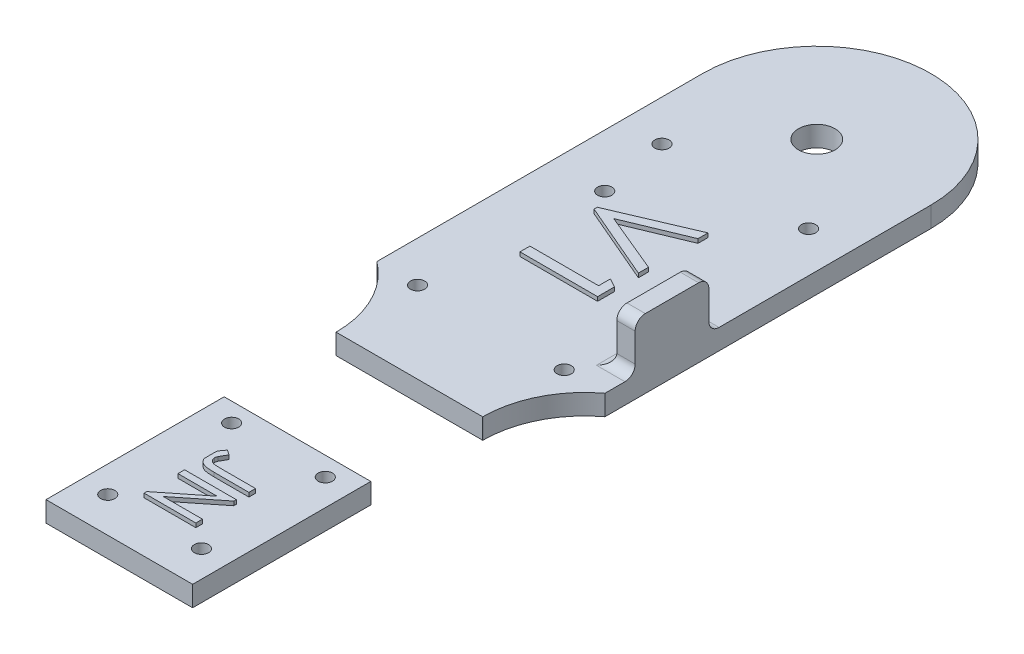
SolidWorks part; units mm, degrees
note: The reader was unsure of these and kept them because the rebuilt part matched: shared geometry of "Sketch2<10>".
ref_plane "Front Plane" through (0, 0, 0) normal (0, 0, 1) x (1, 0, 0)
ref_plane "Top Plane" through (0, 0, 0) normal (0, 1, 0) x (1, 0, 0)
ref_plane "Right Plane" through (0, 0, 0) normal (1, 0, 0) x (0, 0, -1)
sketch "Sketch2" plane through (0, 0, 0) normal (0, 1, 0) x (1, 0, 0)
  line L0 (-17.1263, -104.1263) -> (-17.1263, -4.1263)
  line L1 (-27.1263, 95.8737) -> (-27.1263, 15.8741)
  line L2 (18.8737, -104.1263) -> (18.8737, -4.1268)
  line L3 (-27.1263, 95.8737) -> (28.8737, 95.8737)
  line L4 (28.8737, 95.8737) -> (28.8737, 15.8737)
  line L5 (-17.1263, -75.3563) -> (18.8737, -75.3563)
  line L6 (-17.1263, -31.6163) -> (18.8737, -31.6163)
  line L7 (-17.1263, -4.1363) -> (18.8737, -4.1363)
  line L8 (-5.4644, -31.6163) -> (-5.4644, -75.3563)
  line L9 (-10.6263, 95.8737) -> (-10.6263, -4.1363)
  line L10 (8.4237, 61.6216) -> (8.4237, 59.164)
  line L11 (8.4237, 59.164) -> (-6.1882, 53.0849)
  line L12 (-6.1882, 53.0849) -> (8.4237, 47.0097)
  line L13 (8.4237, 47.0097) -> (8.4237, 44.5254)
  line L14 (8.4237, 44.5254) -> (-10.6263, 52.6957)
  line L15 (-10.6263, 52.6957) -> (-10.6263, 53.478)
  line L16 (-10.6263, 53.478) -> (8.4237, 61.6216)
  line L17 (8.4237, 38.6562) -> (8.4237, 34.512)
  line L18 (8.4237, 34.512) -> (-10.6263, 34.512)
  line L19 (-10.6263, 34.512) -> (-10.6263, 36.9543)
  line L20 (-10.6263, 36.9543) -> (6.2256, 36.9543)
  line L21 (6.2256, 36.9543) -> (6.2256, 39.885)
  line L22 (6.2256, 39.885) -> (8.4237, 38.6562)
  line L23 (7.2356, -48.2761) -> (7.2356, -49.9043)
  line L24 (7.2356, -49.9043) -> (-1.2896, -49.9043)
  line L25 (-4.3552, -43.5543) -> (-3.1849, -44.3607)
  line L26 (-1.259, -48.2761) -> (7.2356, -48.2761)
  line L27 (-5.4644, -52.9978) -> (7.2356, -52.9978)
  line L28 (7.2356, -52.9978) -> (7.2356, -53.6008)
  line L29 (7.2356, -53.6008) -> (-2.414, -61.3017)
  line L30 (-2.414, -61.3017) -> (7.2356, -61.3017)
  line L31 (7.2356, -61.3017) -> (7.2356, -62.9299)
  line L32 (7.2356, -62.9299) -> (-5.4644, -62.9299)
  line L33 (-5.4644, -62.9299) -> (-5.4644, -62.2634)
  line L34 (-5.4644, -62.2634) -> (4.1598, -54.6261)
  line L35 (4.1598, -54.6261) -> (-5.4644, -54.6261)
  line L36 (-5.4644, -54.6261) -> (-5.4644, -52.9978)
  arc A0 (18.8737, -104.1263) -> (-17.1263, -104.1263) centre (0.8737, -104.1263) cw
  arc A1 (28.8737, 95.8737) -> (-27.1263, 95.8737) centre (0.8737, 95.8737) ccw
  circle A2 centre (0.8737, 95.8737) radius 4.5
  arc A7 (-17.1263, -4.1263) -> (-27.1263, 15.8741) centre (-42.1272, -4.1263) ccw
  arc A8 (18.8737, -4.1268) -> (28.8737, 15.8737) centre (43.8746, -4.1268) cw
  circle A9 centre (0.8737, -104.1263) radius 4
  circle A24 centre (-10.6263, -66.6963) radius 1.75
  circle A25 centre (12.3737, -66.6963) radius 1.75
  circle A26 centre (-10.6263, -36.2863) radius 1.75
  circle A27 centre (12.3737, -36.2863) radius 1.75
  circle A28 centre (-17.1263, 15.8637) radius 1.75
  circle A29 centre (18.8737, 15.8637) radius 1.75
  circle A30 centre (-17.1263, 75.8637) radius 1.75
  circle A31 centre (18.8737, 75.8637) radius 1.75
  circle A32 centre (-14.1263, 58.8137) radius 1.75
  spline S0 degree 3 poles (-1.2896, -49.9043) (-1.5863, -49.9012) (-2.0144, -49.9001) (-2.5595, -49.8636) (-2.9158, -49.8305) (-3.237, -49.7918) (-3.5233, -49.7412) (-3.7736, -49.6815) (-4.0586, -49.5871) (-4.3766, -49.4337) (-4.7216, -49.1959) (-5.0282, -48.8992) (-5.2518, -48.6112) (-5.4066, -48.3548) (-5.5104, -48.1503) (-5.5986, -47.9345) (-5.6653, -47.7071) (-5.7224, -47.4697) (-5.7774, -47.1326) (-5.7894, -46.872) (-5.79, -46.6962) knots 0 0 0 0 0.139694 0.201274 0.256981 0.308059 0.353457 0.393717 0.429049 0.494549 0.55908 0.625402 0.694521 0.72997 0.766196 0.802356 0.839468 0.877602 0.917224 1 1 1 1
  spline S1 degree 3 poles (-5.79, -46.6962) (-5.7918, -46.4434) (-5.7523, -46.0643) (-5.6301, -45.5705) (-5.4977, -45.1976) (-5.3107, -44.814) (-4.9452, -44.2475) (-4.6085, -43.8323) (-4.3552, -43.5543) knots 0 0 0 0 0.213832 0.321108 0.430122 0.5483 0.681573 1 1 1 1
  spline S2 degree 3 poles (-3.1849, -44.3607) (-3.2992, -44.5416) (-3.4599, -44.8051) (-3.6615, -45.1433) (-3.7904, -45.3672) (-3.903, -45.5713) (-4.0297, -45.8009) (-4.1084, -45.967) (-4.1567, -46.0703) knots 0 0 0 0 0.326189 0.470537 0.600273 0.720074 0.825942 1 1 1 1
  spline S3 degree 3 poles (-4.1567, -46.0703) (-4.2093, -46.1841) (-4.2862, -46.404) (-4.326, -46.6342) (-4.3246, -46.742) knots 0 0 0 0 0.538549 1 1 1 1
  spline S4 degree 3 poles (-4.3246, -46.742) (-4.3246, -46.8918) (-4.2907, -47.1171) (-4.1676, -47.3938) (-4.0442, -47.5889) (-3.8873, -47.7643) (-3.6989, -47.9109) (-3.4878, -48.0346) (-3.2864, -48.1099) (-3.1018, -48.1618) (-2.9291, -48.1885) (-2.7269, -48.219) (-2.493, -48.2361) (-2.2285, -48.2552) (-1.8138, -48.2719) (-1.4872, -48.2761) (-1.259, -48.2761) knots 0 0 0 0 0.116094 0.173422 0.233343 0.294244 0.354534 0.417481 0.482953 0.520381 0.565714 0.61808 0.678709 0.747142 0.823369 1 1 1 1
  point P127 (-44.7307, 83.3505)
  dimension "D1" = 28
  dimension "D3" = 8.66
  dimension "D13" = 27.48
  dimension "D4" = 6.5
  dimension "D5" = 6.5
  dimension "D6" = 4.67
  dimension "D11" = 10
  dimension "D14" = 20
  dimension "D15" = 20
  dimension "D16" = 10
  dimension "D17" = 60
  dimension "D18" = 15
  dimension "D2" = 28.77
  dimension "D7" = 100
  dimension "D8" = 200
  dimension "D9" = 36
  dimension "D10" = 18
  dimension "D12" = 43.74
  dimension "D19" = 37.06
extrude "Boss-Extrude5" add sketch "Sketch2" along normal blind 5
extrude "Boss-Extrude6" add sketch "Sketch2<10>" along normal blind 6 contours L35 L34 L8 L32 L31 L30 L29 L28 L27 | S4 S3 S2 L25 S1 L8 S0 L24 L23 L26 | L22 L21 L20 L9 L18 L17 | L16 L9 L14 L13 L12 L11 L10
sketch "Sketch2<10>" plane through (0, 0, 0) normal (0, 1, 0) x (1, 0, 0) same geometry as "Sketch2"
sketch "Sketch3" plane through (0, 5, 0) normal (0, 1, 0) x (1, 0, 0)
  line L0 (28.8737, 95.8737) -> (28.8737, 15.8737) construction
  line L1 (28.8737, 41.3737) -> (24.3737, 41.3737)
  line L2 (28.8737, 41.3737) -> (28.8737, 23.2807)
  line L3 (28.8737, 23.2807) -> (24.3737, 23.2807)
  line L4 (24.3737, 41.3737) -> (24.3737, 23.2807)
  dimension "D1" = 4.5
extrude "Boss-Extrude7" add sketch "Sketch3" along normal blind 12
fillet "Fillet1" radius 2.5 5 edges at (26.6237, 5, -41.3737) (26.6237, 17, -41.3737) (26.6237, 5, -23.2807) (26.6237, 17, -23.2807) (24.3737, 5, -32.3272)
